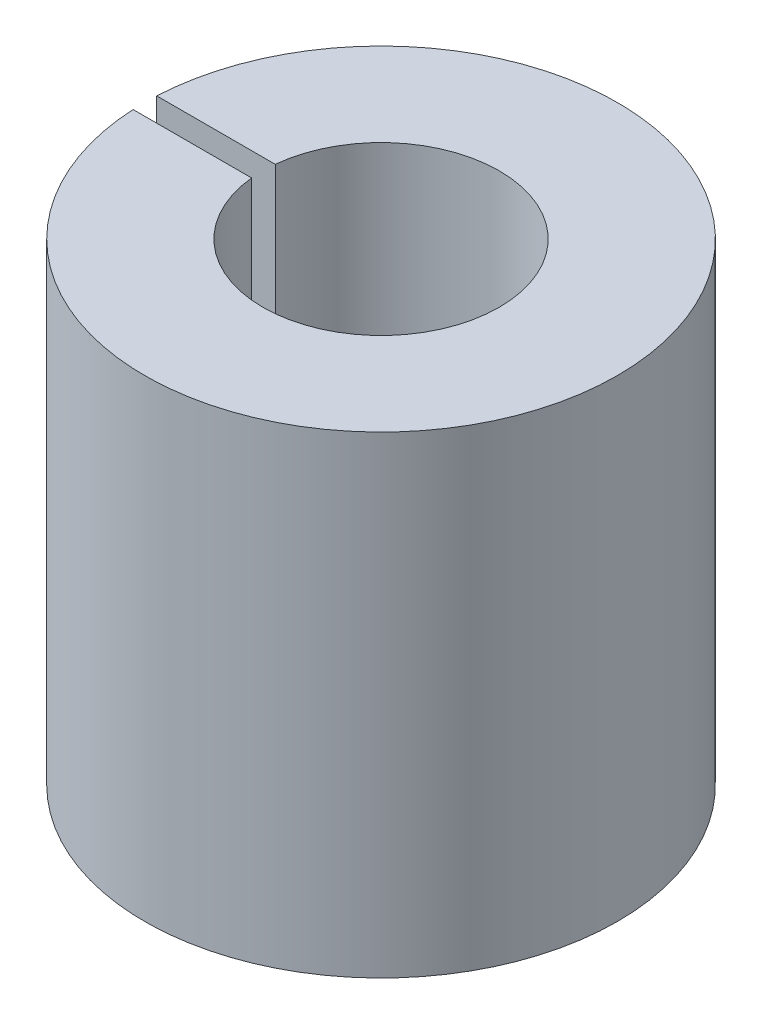
SolidWorks part; units mm, degrees
ref_plane "Plan de face" through (0, 0, 0) normal (0, 0, 1) x (1, 0, 0)
ref_plane "Plan de dessus" through (0, 0, 0) normal (0, 1, 0) x (1, 0, 0)
ref_plane "Plan de droite" through (0, 0, 0) normal (1, 0, 0) x (0, 0, -1)
sketch "Esquisse2" plane through (0, 0, 0) normal (0, 1, 0) x (1, 0, 0)
  circle A0 centre (0, 0) radius 2.5
  circle A1 centre (0, 0) radius 5
extrude "Boss.-Extru.1" add sketch "Esquisse2" along normal blind 10 contours A1
extrude "Enlèv. mat.-Extru.2" cut sketch "Esquisse2<5>" along normal blind 80 contours A0 region at (0, 0, 0)
sketch "Esquisse2<5>" plane through (0, 0, 0) normal (0, 1, 0) x (1, 0, 0) same geometry as "Esquisse2"
sketch "Esquisse3" plane through (0, 10, 0) normal (0, 1, 0) x (1, 0, 0)
  line L21 (0, 0) -> (-5, 0)
  line L23 (-5.9257, 0.25) -> (-1.3702, 0.25)
  line L24 (-5.9257, 0.25) -> (-5.9257, -0.25)
  line L25 (-5.9257, -0.25) -> (-1.3702, -0.25)
  line L26 (-1.3702, 0.25) -> (-1.3702, -0.25)
  line L27 (-5.9257, 0.25) -> (-1.3702, -0.25) construction
  line L28 (-5.9257, -0.25) -> (-1.3702, 0.25) construction
  circle A0 centre (0, 0) radius 5 construction
  point P4 (-3.648, 0)
  dimension "D1" = 0.5
extrude "Enlèv. mat.-Extru.10" cut sketch "Esquisse3" against normal blind 80 contours L23 L26 L25 L24
